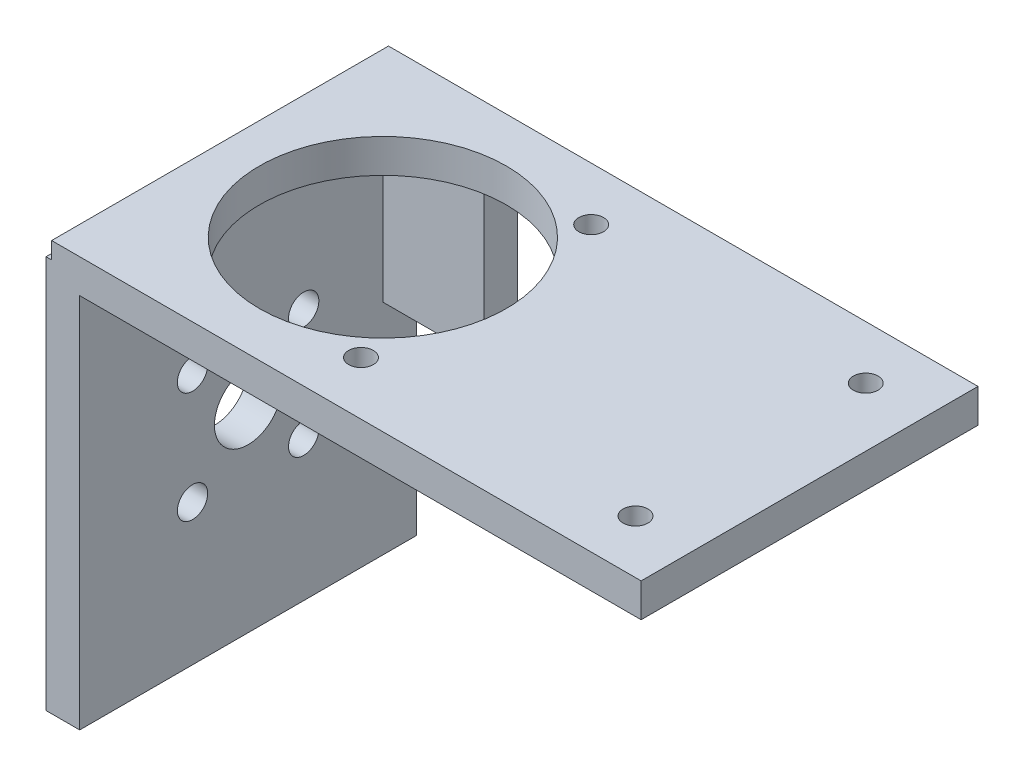
SolidWorks part; units mm, degrees
ref_plane "Front Plane" through (0, 0, 0) normal (0, 0, 1) x (1, 0, 0)
ref_plane "Top Plane" through (0, 0, 0) normal (0, 1, 0) x (1, 0, 0)
ref_plane "Right Plane" through (0, 0, 0) normal (1, 0, 0) x (0, 0, -1)
ref_plane "PZ_m15_000" through (0, 0, -15) normal (0, 0, 1) x (1, 0, 0)
sketch "S_box1" plane through (0, 0, -15) normal (0, 0, 1) x (1, 0, 0)
  line L0 (-15, -17.5) -> (-12, -17.5)
  line L1 (-12, -17.5) -> (-12, 17.5)
  line L2 (-12, 17.5) -> (-15, 17.5)
  line L3 (-15, 17.5) -> (-15, -17.5)
  dimension "P1" = 15
  dimension "P2" = 17.5
  dimension "P3" = 12
  dimension "P4" = 17.5
  dimension "P5" = 12
  dimension "P6" = 17.5
  dimension "P7" = 15
  dimension "P8" = 17.5
extrude "Boss_1" add sketch "S_box1" along normal blind 30
sketch "S_box2" plane through (0, 0, -15) normal (0, 0, 1) x (1, 0, 0)
  line L0 (-14.5, 16) -> (38, 16)
  line L1 (38, 16) -> (38, 19)
  line L2 (38, 19) -> (-14.5, 19)
  line L3 (-14.5, 19) -> (-14.5, 16)
  dimension "P1" = 14.5
  dimension "P2" = 16
  dimension "P3" = 38
  dimension "P4" = 16
  dimension "P5" = 38
  dimension "P6" = 19
  dimension "P7" = 14.5
  dimension "P8" = 19
extrude "Boss_2" add sketch "S_box2" along normal blind 30
sketch "S_box3" plane through (0, 0, -15) normal (0, 0, 1) x (1, 0, 0)
  line L0 (-14.5, 2) -> (-3, 2)
  line L1 (-3, 2) -> (-3, 18.5)
  line L2 (-3, 18.5) -> (-14.5, 18.5)
  line L3 (-14.5, 18.5) -> (-14.5, 2)
  dimension "P1" = 14.5
  dimension "P2" = 2
  dimension "P3" = 3
  dimension "P4" = 2
  dimension "P5" = 3
  dimension "P6" = 18.5
  dimension "P7" = 14.5
  dimension "P8" = 18.5
extrude "Boss_3" add sketch "S_box3" along normal blind 3
ref_plane "PX_m15_100" through (-15.1, 0, 0) normal (1, 0, 0) x (0, 0, -1)
sketch "S_hole4" plane through (-15.1, 0, 0) normal (1, 0, 0) x (0, 0, -1)
  circle A0 centre (0, 0) radius 3
  dimension "D1_S_hole4" = 6
extrude "Hole_4" cut sketch "S_hole4" along normal blind 3.2
sketch "S_hole5" plane through (-15.1, 0, 0) normal (1, 0, 0) x (0, 0, -1)
  circle A0 centre (-4.9497, -4.9497) radius 1.35
  dimension "D1_S_hole5" = 2.7
  dimension "P2" = 4.9497
  dimension "P3" = 4.9497
extrude "Hole_5" cut sketch "S_hole5" along normal blind 3.2
sketch "S_hole6" plane through (-15.1, 0, 0) normal (1, 0, 0) x (0, 0, -1)
  circle A0 centre (-4.9497, 4.9497) radius 1.35
  dimension "D1_S_hole6" = 2.7
  dimension "P2" = 4.9497
  dimension "P3" = 4.9497
extrude "Hole_6" cut sketch "S_hole6" along normal blind 3.2
sketch "S_hole7" plane through (-15.1, 0, 0) normal (1, 0, 0) x (0, 0, -1)
  circle A0 centre (4.9497, 4.9497) radius 1.35
  dimension "D1_S_hole7" = 2.7
  dimension "P2" = 4.9497
  dimension "P3" = 4.9497
extrude "Hole_7" cut sketch "S_hole7" along normal blind 3.2
sketch "S_hole8" plane through (-15.1, 0, 0) normal (1, 0, 0) x (0, 0, -1)
  circle A0 centre (4.9497, -4.9497) radius 1.35
  dimension "D1_S_hole8" = 2.7
  dimension "P2" = 4.9497
  dimension "P3" = 4.9497
extrude "Hole_8" cut sketch "S_hole8" along normal blind 3.2
ref_plane "PY_p15_900" through (0, 15.9, 0) normal (0, 1, 0) x (1, 0, 0)
sketch "S_hole9" plane through (0, 15.9, 0) normal (0, 1, 0) x (1, 0, 0)
  circle A0 centre (0, 0) radius 11
  dimension "D1_S_hole9" = 22
extrude "Hole_9" cut sketch "S_hole9" along normal blind 3.2
sketch "S_hole10" plane through (0, 15.9, 0) normal (0, 1, 0) x (1, 0, 0)
  circle A0 centre (8.3, 10.25) radius 1.1
  dimension "D1_S_hole10" = 2.2
  dimension "P2" = 8.3
  dimension "P3" = 10.25
extrude "Hole_10" cut sketch "S_hole10" along normal blind 3.2
sketch "S_hole11" plane through (0, 15.9, 0) normal (0, 1, 0) x (1, 0, 0)
  circle A0 centre (8.3, -10.25) radius 1.1
  dimension "D1_S_hole11" = 2.2
  dimension "P2" = 8.3
  dimension "P3" = 10.25
extrude "Hole_11" cut sketch "S_hole11" along normal blind 3.2
sketch "S_hole12" plane through (0, 15.9, 0) normal (0, 1, 0) x (1, 0, 0)
  circle A0 centre (32.75, 10.25) radius 1.1
  dimension "D1_S_hole12" = 2.2
  dimension "P2" = 32.75
  dimension "P3" = 10.25
extrude "Hole_12" cut sketch "S_hole12" along normal blind 3.2
sketch "S_hole13" plane through (0, 15.9, 0) normal (0, 1, 0) x (1, 0, 0)
  circle A0 centre (32.75, -10.25) radius 1.1
  dimension "D1_S_hole13" = 2.2
  dimension "P2" = 32.75
  dimension "P3" = 10.25
extrude "Hole_13" cut sketch "S_hole13" along normal blind 3.2
equation "\"plate_t\" = 3"
equation "\"clearance\" = 0.4"
